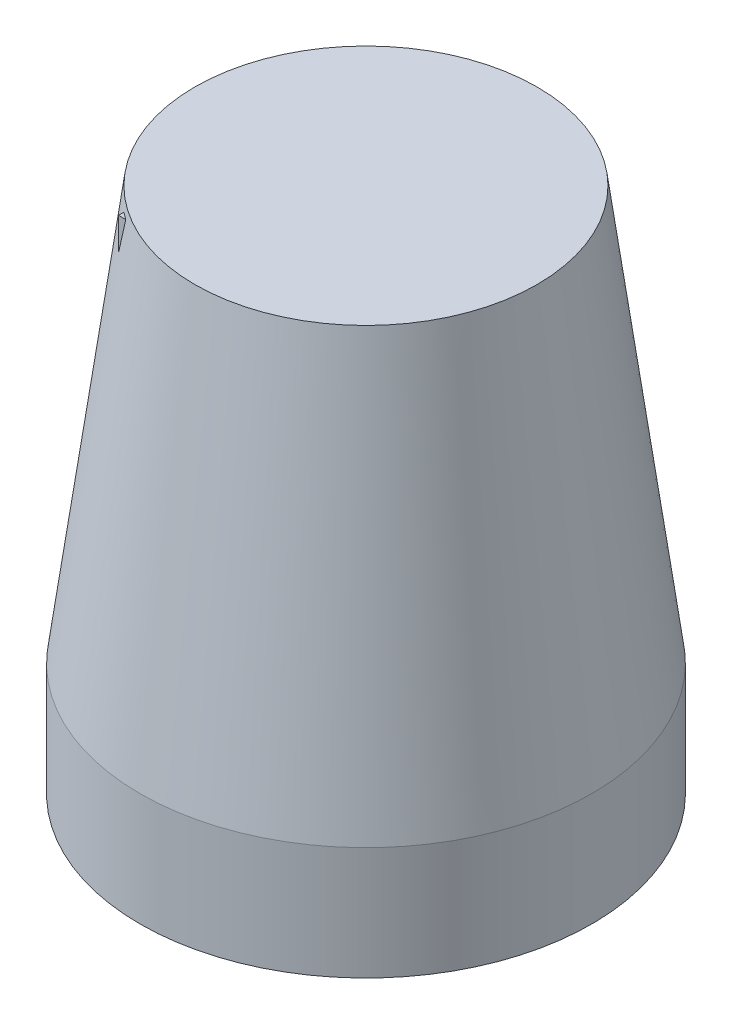
SolidWorks part; units mm, degrees
ref_plane "Front Plane" through (0, 0, 0) normal (0, 0, 1) x (1, 0, 0)
ref_plane "Top Plane" through (0, 0, 0) normal (0, 1, 0) x (1, 0, 0)
ref_plane "Right Plane" through (0, 0, 0) normal (1, 0, 0) x (0, 0, -1)
sketch "Sketch1" plane through (0, 0, 0) normal (0, 1, 0) x (1, 0, 0)
  circle A1 centre (0, 0) radius 6.604
  circle A2 centre (0, 0) radius 5.0038
  dimension "D1" = 10.0076
  dimension "D2" = 13.208
extrude "Boss-Extrude1" add sketch "Sketch1" along normal blind 12.0904 contours A2
loft "Loft1" add section "Sketch1<5>" section edge at (0, 12.0904, 5.0038)
sketch "Sketch1<5>" plane through (0, 0, 0) normal (0, 1, 0) x (1, 0, 0) same geometry as "Sketch1"
extrude "Boss-Extrude2" add sketch "Sketch1<6>" against normal blind 3.302 contours A1
sketch "Sketch1<6>" plane through (0, 0, 0) normal (0, 1, 0) x (1, 0, 0) same geometry as "Sketch1"
sketch "Sketch2" plane through (0, -3.302, 0) normal (0, -1, 0) x (1, 0, 0)
  circle A0 centre (0, 0) radius 2.9972
  dimension "D1" = 5.9944
extrude "Cut-Extrude1" cut sketch "Sketch2" against normal blind 11.43
sketch "Sketch3" plane through (0, -3.302, 0) normal (0, -1, 0) x (1, 0, 0)
  circle A0 centre (0, 0) radius 5.2705
  dimension "D1" = 10.541
extrude "Cut-Extrude2" cut sketch "Sketch3" against normal blind 2.9464
sketch "Sketch4" plane through (0, -0.3556, 0) normal (0, -1, 0) x (1, 0, 0)
  line L1 (-1.4986, 4.1117) -> (-3.122, 4.1117)
  line L2 (-1.4986, 4.1117) -> (-1.4986, -2.648)
  line L3 (-1.4986, -2.648) -> (-3.122, -2.648)
  line L4 (-3.122, 4.1117) -> (-3.122, -2.648)
  circle A0 centre (0, 0) radius 2.9972 construction
  dimension "D1" = 1.4986
extrude "Boss-Extrude3" add sketch "Sketch4" against normal blind 12.192
